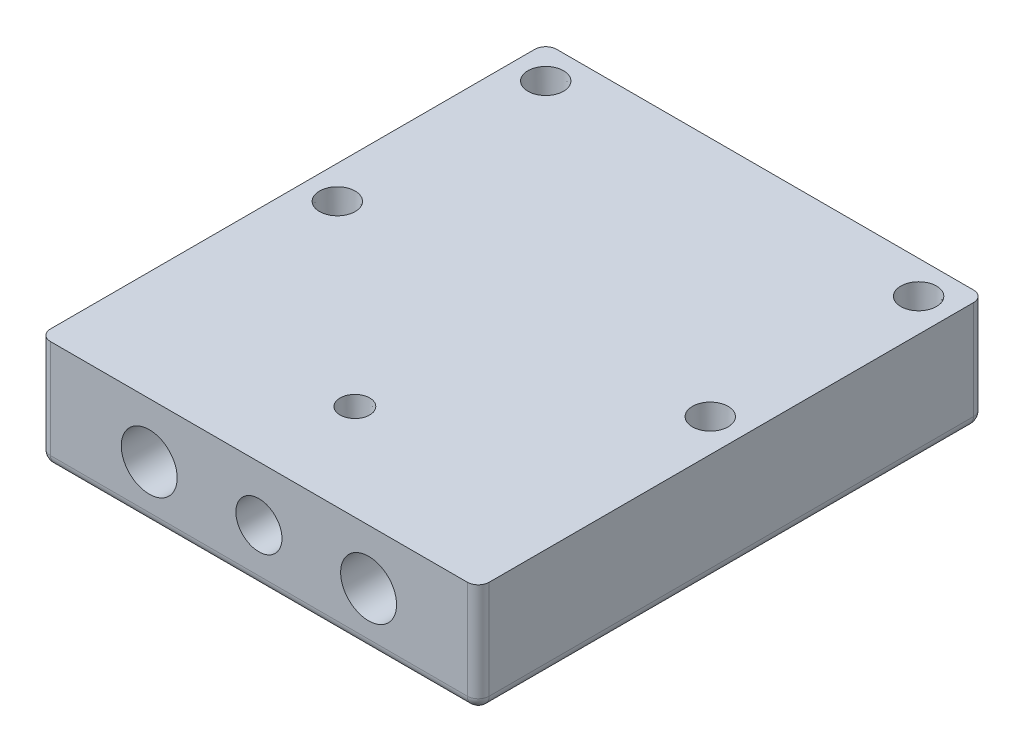
SolidWorks part; units mm, degrees
ref_plane "Front Plane" through (0, 0, 0) normal (0, 0, 1) x (1, 0, 0)
ref_plane "Top Plane" through (0, 0, 0) normal (0, 1, 0) x (1, 0, 0)
ref_plane "Right Plane" through (0, 0, 0) normal (1, 0, 0) x (0, 0, -1)
sketch "Sketch1" plane through (0, 0, 0) normal (0, 1, 0) x (1, 0, 0)
  line L1 (-40, 46.15) -> (40, 46.15)
  line L2 (-40, 46.15) -> (-40, -46.15)
  line L3 (-40, -46.15) -> (40, -46.15)
  line L4 (40, 46.15) -> (40, -46.15)
  line L5 (-40, 46.15) -> (40, -46.15) construction
  line L6 (-40, -46.15) -> (40, 46.15) construction
  point P0 (0, 0)
  dimension "D1" = 92.3
  dimension "D2" = 80
extrude "Boss-Extrude1" add sketch "Sketch1" along normal blind 20
hole_wizard "Hole1" positions "Sketch2" profile "Sketch3" legacy end condition through all
sketch "Sketch2" plane through (0, 20, 0) normal (0, 1, 0) x (1, 0, 0)
  line L0 (-34, 40.15) -> (-34, 2.15) construction
  line L1 (-34, 2.15) -> (34, 2.15) construction
  line L2 (34, 2.15) -> (34, 40.15) construction
  line L3 (34, 40.15) -> (-34, 40.15) construction
  line L5 (40, 46.15) -> (-40, 46.15) construction
  line L6 (-40, 46.15) -> (-40, -46.15) construction
  point P0 (-34, 40.15)
  point P2 (34, 40.15)
  point P4 (34, 2.15)
  point P6 (-34, 2.15)
  point P19 (0, 46.15)
  point P20 (0, 40.15)
  dimension "D1" = 6
  dimension "D2" = 6
  dimension "D3" = 38
sketch "Sketch3" plane through (-34, 20, -40.15) normal (1, 0, 0) x (0, 0, 1)
  line L0 (0, 0) -> (0, 20)
  line L1 (0, 20) -> (2.9, 20)
  line L2 (2.9, 20) -> (2.9, 6)
  line L3 (2.9, 6) -> (3.25, 6)
  line L4 (3.25, 6) -> (3.25, 0)
  line L5 (3.25, 0) -> (0, 0)
  line L6 (0, 110) -> (0, -10) construction
  dimension "Diameter" = 5.8
  dimension "Depth" = 20
  dimension "C-Bore Diameter" = 6.5
  dimension "C-Bore Depth" = 6
chamfer "Chamfer1" distance 6 distance2 0.35 4 edges at (-34, 14, 1.1) (34, 14, 1.1) (34, 14, -36.9) (-34, 14, -36.9) first distance on face at (-34, 14, 1.1) first distance on face at (34, 14, 1.1) first distance on face at (34, 14, -36.9) first distance on face at (-34, 14, -36.9)
sketch "Sketch4" plane through (0, 0, 46.15) normal (0, 0, 1) x (1, 0, 0)
  line L0 (-40, 20) -> (-40, 0) construction
  line L1 (-20, 10) -> (0, 10) construction
  line L2 (0, 10) -> (20, 10) construction
  circle A0 centre (0, 10) radius 4.2
  circle A1 centre (-20, 10) radius 5.1
  circle A2 centre (20, 10) radius 5.1
  point P6 (-40, 10)
  dimension "D1" = 8.4
  dimension "D2" = 10.2
  dimension "D3" = 20
extrude "Cut-Extrude1" cut sketch "Sketch4" against normal through all
hole_wizard "Hole2" positions "Sketch5" profile "Sketch6" legacy end condition through all
sketch "Sketch5" plane through (-40, 0, 0) normal (0, 1, 0) x (0, 0, 1)
  line L1 (46.15, 0) -> (46.15, 80) construction
  point P0 (28.65, 40)
  point P8 (46.15, 40)
  dimension "D1" = 17.5
sketch "Sketch6" plane through (0, 0, 28.65) normal (1, 0, 0) x (0, 0, -1)
  line L0 (0, 0) -> (0, 20)
  line L1 (0, 20) -> (2.4, 20)
  line L2 (2.4, 20) -> (2.4, 4)
  line L3 (2.4, 4) -> (2.7, 4)
  line L4 (2.7, 4) -> (2.7, 0)
  line L5 (2.7, 0) -> (0, 0)
  line L6 (0, 110) -> (0, -10) construction
  dimension "Diameter" = 4.8
  dimension "Depth" = 20
  dimension "C-Bore Diameter" = 5.4
  dimension "C-Bore Depth" = 4
chamfer "Chamfer2" distance 4 distance2 0.3 1 edges at (0, 4, 25.95) first distance on face at (0, 4, 25.95)
ref_plane "Plane1" through (0, 10, 0) normal (0, 1, 0) x (1, 0, 0)
mirror "Mirror1" about plane through (0, 10, 0) normal (0, 1, 0) of "Hole2", "Chamfer2"
fillet "Fillet1" radius 2 8 edges at (0, 0, -46.15) (40, 10, -46.15) (40, 0, 0) (0, 0, 46.15) (-40, 0, 0) (-40, 10, -46.15) (40, 10, 46.15) (-40, 10, 46.15)
